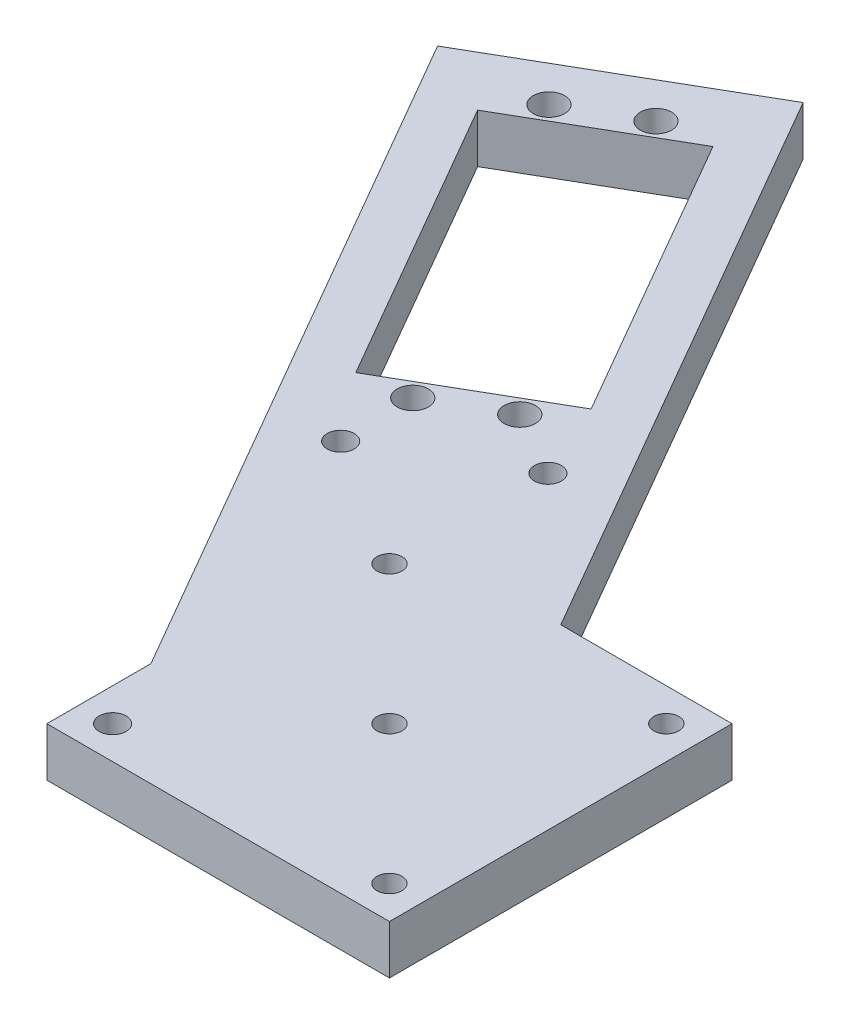
SolidWorks part; units mm, degrees
ref_plane "Front Plane" through (0, 0, 0) normal (0, 0, 1) x (1, 0, 0)
ref_plane "Top Plane" through (0, 0, 0) normal (0, 1, 0) x (1, 0, 0)
ref_plane "Right Plane" through (0, 0, 0) normal (1, 0, 0) x (0, 0, -1)
sketch "Sketch1" plane through (0, 0, 0) normal (0, 1, 0) x (1, 0, 0)
  line L0 (-22.0937, -22.0937) -> (22.3563, -22.0937)
  line L5 (22.3563, -22.0937) -> (22.3563, 22.3563)
  line L6 (22.3563, 22.3563) -> (-22.0937, 22.3563)
  line L7 (-22.0937, 22.3563) -> (-22.0937, -22.0937)
  line L8 (-72.8937, 79.3984) -> (-22.0937, -8.5898)
  line L9 (-42.8249, 96.7586) -> (0.1313, 22.3563)
  line L10 (-42.8249, 96.7586) -> (-72.8937, 79.3984)
  line L11 (22.3563, 22.3563) -> (-22.0937, -22.0937) construction
  line L12 (-34.7683, 28.7038) -> (-17.7238, 38.5444) construction
  circle A0 centre (-17.8292, 18.0918) radius 1.625
  circle A1 centre (0.1313, 0.1313) radius 1.625
  circle A2 centre (18.0918, -17.8292) radius 1.625
  circle A3 centre (-17.8292, -17.8292) radius 1.75
  circle A4 centre (18.0918, 18.0918) radius 1.625
  circle A5 centre (-34.7683, 28.7038) radius 1.7499
  circle A6 centre (-17.7238, 38.5444) radius 1.75
  point P22 (-17.8292, 38.5444)
  dimension "D6" = 3.5
  dimension "D7" = 3.4999
  dimension "D1" = 101.6
  dimension "D2" = 30
  dimension "D3" = 90
  dimension "D4" = 44.45
  dimension "D5" = 38.1
  dimension "D9" = 6.3475
  dimension "D10" = 12.6746
extrude "Boss-Extrude1" add sketch "Sketch1" along normal blind 6.35 contours L10 L7 L6 | L6 L7 L0 L5 A4 A3 A2 A1 A0 | L5 L11 A4 A1 A3 L0 A2 region at (-21.4651, 0, 15.3417) region at (-37.2316, 0, -51.408)
sketch "Sketch2" plane through (0, 0, 0) normal (0, -1, 0) x (1, 0, 0)
  line L4 (-59.0837, -80.0393) -> (-34.9537, -38.2449) construction
  line L5 (-34.9537, -38.2449) -> (-26.1549, -43.3249) construction
  line L6 (-26.1549, -43.3249) -> (-50.2849, -85.1193) construction
  line L7 (-50.2849, -85.1193) -> (-59.0837, -80.0393) construction
  line L8 (-72.8937, -79.3984) -> (-22.0937, 8.5898) construction
  line L9 (-54.6843, -82.5793) -> (-57.8593, -88.0785) construction
  line L10 (-42.8249, -96.7586) -> (-72.8937, -79.3984) construction
  line L11 (-41.503, -37.3966) -> (-63.093, -74.7916)
  line L12 (-41.503, -37.3966) -> (-22.1456, -48.5726)
  line L13 (-63.093, -74.7916) -> (-43.7356, -85.9676)
  line L14 (-22.1456, -48.5726) -> (-43.7356, -85.9676)
  line L15 (-41.503, -37.3966) -> (-43.7356, -85.9676) construction
  line L16 (-63.093, -74.7916) -> (-22.1456, -48.5726) construction
  line L17 (-42.6193, -61.6821) -> (-47.0187, -59.1421) construction
  line L18 (-54.6843, -82.5793) -> (-53.4143, -80.3796) construction
  circle A2 centre (-59.0837, -80.0393) radius 2.032
  circle A3 centre (-50.2849, -85.1193) radius 2.032
  circle A4 centre (-26.1549, -43.3249) radius 2.032
  circle A5 centre (-34.9537, -38.2449) radius 2.032
  point P15 (-42.6193, -61.6821)
  circle M24 centre (-17.7238, -38.5444) radius 1.75
  dimension "D3" = 4.064
  dimension "D1" = 48.26
  dimension "D2" = 10.16
  dimension "D4" = 6.35
  dimension "D5" = 22.352
  dimension "D6" = 43.18
extrude "Cut-Extrude1" cut sketch "Sketch2" against normal through all contours L7 A3 L6 | L6 A3 L7 | L4 A2 L7 | L7 A2 L4 | L6 A4 L5 | L5 A4 L6 | L5 A5 L4 | L4 A5 L5 | L14 L12 L11 L13 M24 region at (-42.6193, 0, -61.6821) region at (-59.0837, 0, -80.0393) region at (-50.2849, 0, -85.1193) region at (-26.1549, 0, -43.3249) region at (-34.9537, 0, -38.2449)
